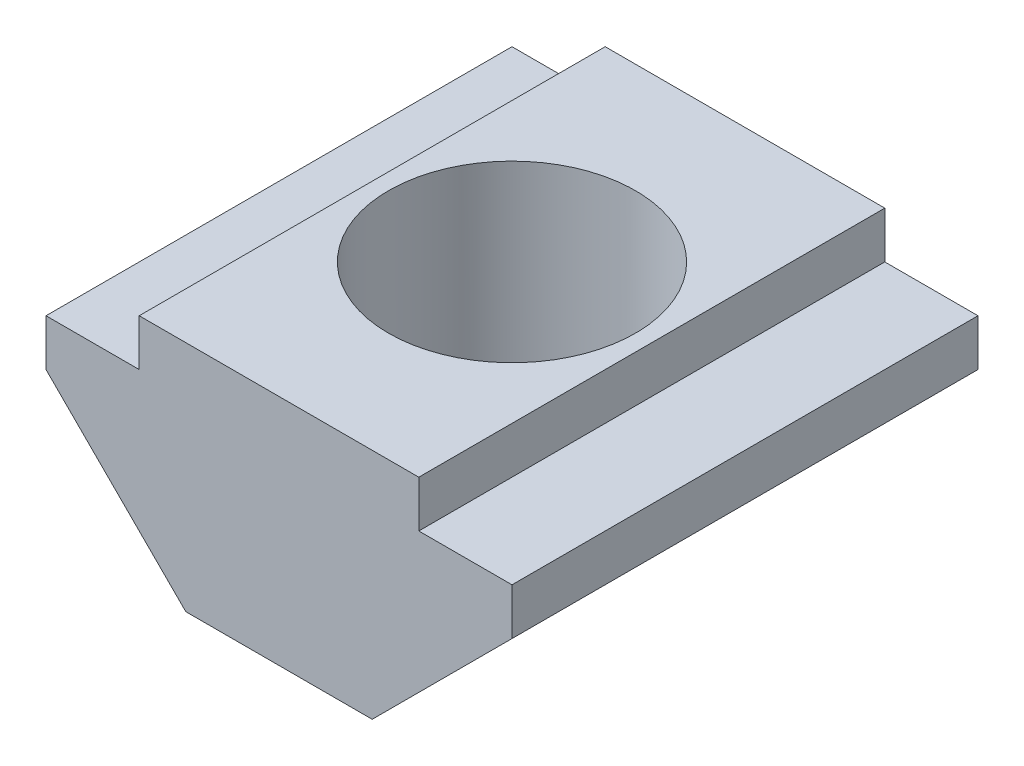
SolidWorks part; units mm, degrees
ref_plane "Front Plane" through (0, 0, 0) normal (0, 0, 1) x (1, 0, 0)
ref_plane "Top Plane" through (0, 0, 0) normal (0, 1, 0) x (1, 0, 0)
ref_plane "Right Plane" through (0, 0, 0) normal (1, 0, 0) x (0, 0, -1)
sketch "Sketch1" plane through (0, 0, 0) normal (0, 0, 1) x (1, 0, 0)
  line L0 (-3, 2.5) -> (3, 2.5)
  line L1 (-5, -2.5) -> (5, -2.5)
  line L2 (-5, -2.5) -> (-5, 2.5)
  line L3 (-5, 2.5) -> (5, 2.5)
  line L4 (5, -2.5) -> (5, 2.5)
  line L5 (-5, -2.5) -> (5, 2.5) construction
  line L6 (-5, 2.5) -> (5, -2.5) construction
  line L7 (-3, 2.5) -> (-3, 1.5)
  line L8 (-3, 1.5) -> (-5, 1.5)
  line L9 (3, 2.5) -> (3, 1.5)
  line L10 (3, 1.5) -> (5, 1.5)
  line L11 (-5, 1.5) -> (-5, 0.5)
  line L12 (5, 1.5) -> (5, 0.5)
  line L13 (-5, 0.5) -> (-2, -2.5)
  line L14 (-2, -2.5) -> (2, -2.5)
  line L15 (2, -2.5) -> (5, 0.5)
  point P0 (0, 0)
  point P8 (0, 2.5)
  dimension "D1" = 5
  dimension "D2" = 10
  dimension "D3" = 6
  dimension "D4" = 1
  dimension "D5" = 1
  dimension "D6" = 45
  dimension "D7" = 45
extrude "Boss-Extrude1" add sketch "Sketch1" along normal blind 5 and the other way blind 5 contours L1 L15 L4 L10 L9 L0 L7 L8 L2 L13 region at (0, 0.1486, 0)
hole_wizard "M5 Clearance Hole1" positions "Sketch3" profile "Sketch4" hole size "M5" standard "ANSI Metric"
sketch "Sketch3" plane through (0, 2.5, 0) normal (0, 1, 0) x (1, 0, 0)
  point P0 (0, 0)
sketch "Sketch4" plane through (0, 2.5, 0) normal (1, 0, 0) x (0, 0, 1)
  line L0 (0, 0) -> (0, 24.6723)
  line L1 (0, 24.6723) -> (2.65, 23.08)
  line L2 (2.65, 23.08) -> (2.65, 0)
  line L5 (2.65, 0) -> (0, 0)
  line L10 (0, 24.6723) -> (-2.65, 23.08) construction
  line L11 (0, -6.35) -> (0, 107.95) construction
  dimension "Hole Dia." = 5.3
  dimension "Hole Depth" = 23.08
  dimension "Drill Angle" = 118
